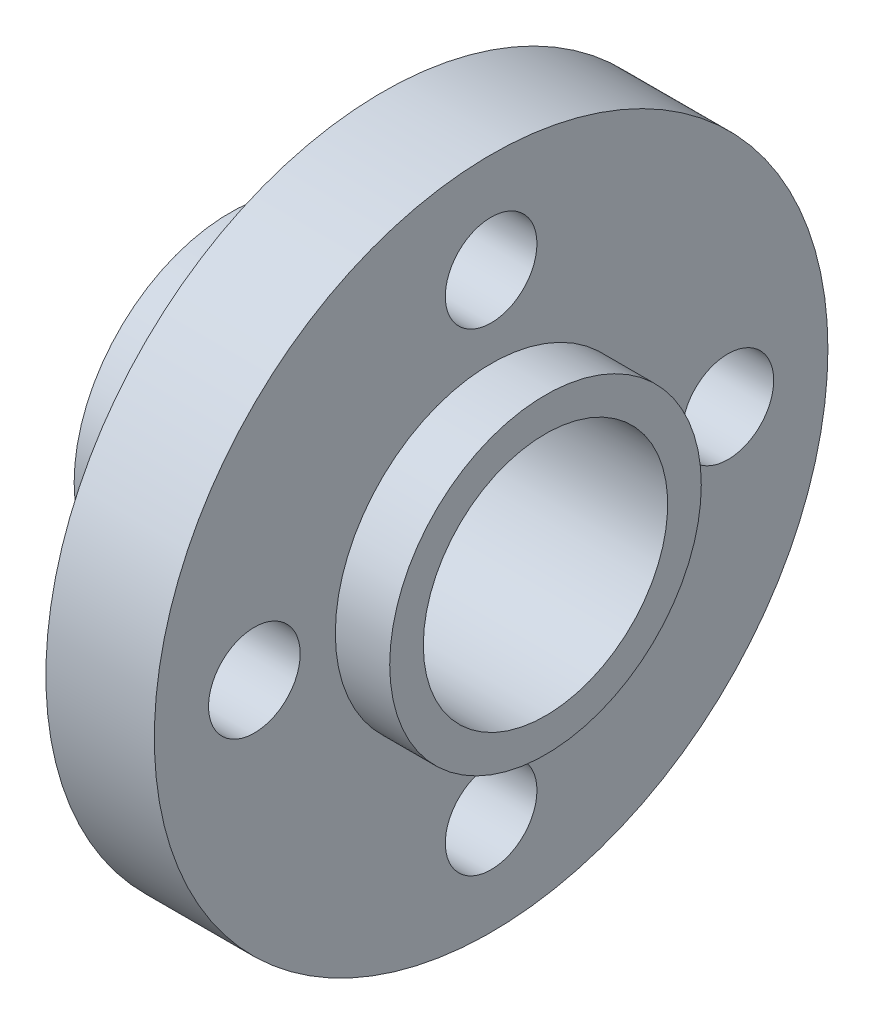
SolidWorks part; units mm, degrees
material "Brass"
ref_plane "Front Plane" through (0, 0, 0) normal (0, 0, 1) x (1, 0, 0)
ref_plane "Top Plane" through (0, 0, 0) normal (0, 1, 0) x (1, 0, 0)
ref_plane "Right Plane" through (0, 0, 0) normal (1, 0, 0) x (0, 0, -1)
sketch "Sketch1" plane through (0, 0, 0) normal (1, 0, 0) x (0, 0, -1)
  circle A0 centre (0, 0) radius 11.025
  dimension "D1" = 22.05
extrude "Boss-Extrude1" add sketch "Sketch1" along normal blind 3.55
sketch "Sketch2" plane through (3.55, 0, 0) normal (1, 0, 0) x (0, 0, -1)
  circle A0 centre (0, 0) radius 5.1
  dimension "D1" = 10.2
extrude "Boss-Extrude2" add sketch "Sketch2" along normal blind 1.78
sketch "Sketch3" plane through (0, 0, 0) normal (-1, 0, 0) x (0, 0, 1)
  circle A0 centre (0, 0) radius 5.1
  dimension "D1" = 10.2
extrude "Boss-Extrude3" add sketch "Sketch3" along normal blind 5
sketch "Sketch5" plane through (-5, 0, 0) normal (-1, 0, 0) x (0, 0, 1)
  circle A0 centre (0, 0) radius 4
  dimension "D1" = 8
extrude "Cut-Extrude1" cut sketch "Sketch5" against normal through all
sketch "Sketch6" plane through (0, 0, 0) normal (-1, 0, 0) x (0, 0, 1)
  circle A0 centre (0, 0) radius 7.75 construction
  circle A1 centre (-7.75, 0) radius 1.5
  dimension "D1" = 15.5
  dimension "D2" = 3
extrude "Cut-Extrude2" cut sketch "Sketch6" against normal through all
pattern_circular "CirPattern1" count 4 over 360 about axis through (0, 0, 0) along (-1, 0, 0) of "Cut-Extrude2"
